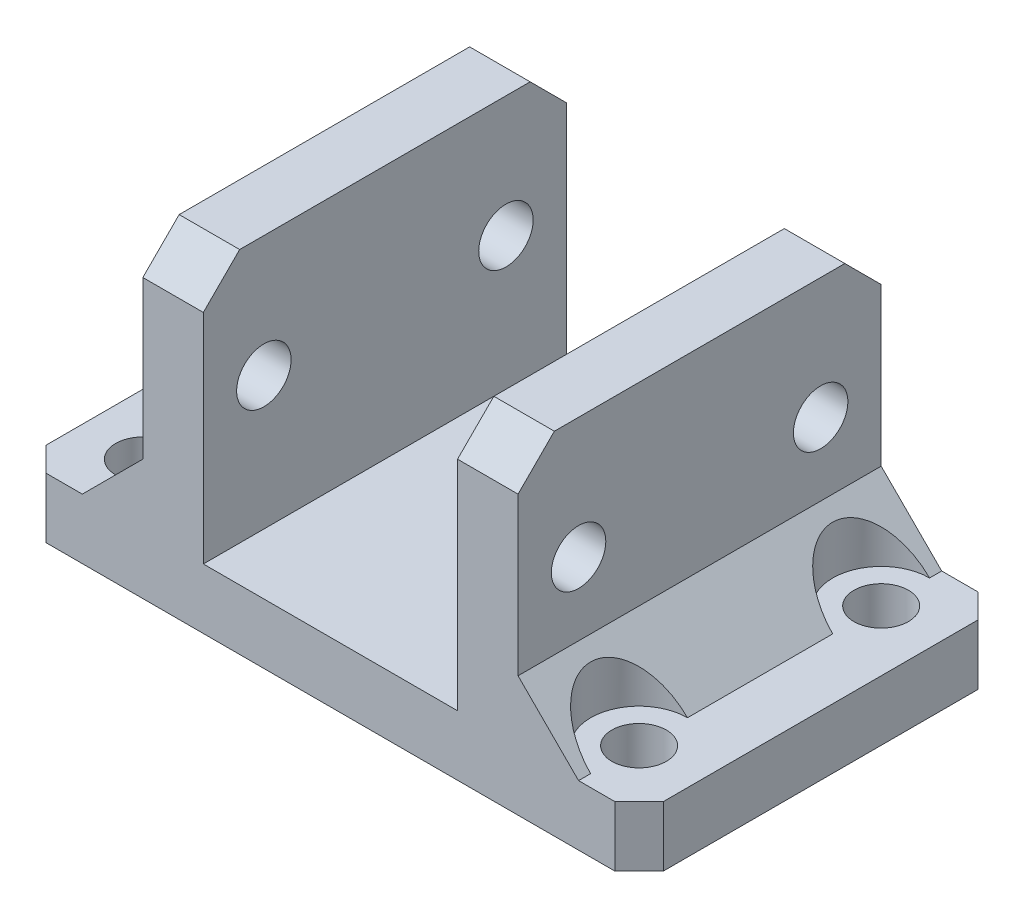
SolidWorks part; units mm, degrees
ref_plane "Front Plane" through (0, 0, 0) normal (0, 0, 1) x (1, 0, 0)
ref_plane "Top Plane" through (0, 0, 0) normal (0, 1, 0) x (1, 0, 0)
ref_plane "Right Plane" through (0, 0, 0) normal (1, 0, 0) x (0, 0, -1)
sketch "Sketch13" plane through (0, 0, 0) normal (0, 0, 1) x (1, 0, 0)
  line L2 (-11, 10) -> (-11, -11)
  line L3 (-11, -11) -> (10, -11)
  line L4 (10, 10) -> (10, -11)
  line L5 (-16, -11) -> (-26, -11)
  line L7 (10, -11) -> (-11, -11)
  line L8 (15, -11) -> (15, 10)
  line L9 (15, 10) -> (10, 10)
  line L10 (-16, -11) -> (-16, 10)
  line L13 (-11, 10) -> (-16, 10)
  line L14 (25, -15.9758) -> (-26, -15.9758)
  line L15 (25, -15.9758) -> (25, -11)
  line L16 (25, -11) -> (15, -11)
  line L17 (-26, -15.9758) -> (-26, -11)
  line L22 (10, -11) -> (-11, -11)
  point P0 (0, 0)
  point P6 (0, 0)
  point P13 (0, -12.4879)
  dimension "D1" = 21
  dimension "D2" = 21
  dimension "D3" = 10
  dimension "D4" = 5
  dimension "D5" = 5
  dimension "D6" = 10
extrude "Boss-Extrude1" add sketch "Sketch13" against normal blind 30 contours L17 L14 L15 L16 L8 L9 L4 L3 L2 L13 L10 L5 region at (-11.5723, -0.5, 0)
sketch "Sketch14" plane through (0, -11, 0) normal (0, 1, 0) x (1, 0, 0)
  line L0 (15, 30) -> (25, 30)
  line L2 (25, 0) -> (15, 0) construction
  line L3 (15, 0) -> (25, 0)
  line L4 (25, 30) -> (25, 0) construction
  line L6 (20, 30) -> (20, 0)
  line L10 (-26, 30) -> (-26, 0) construction
  circle A0 centre (20, 25) radius 2.25
  circle A1 centre (20, 5) radius 2.25
  circle A2 centre (-21, 5) radius 2.25
  circle A3 centre (-21, 25) radius 2.25
  circle A4 centre (20, 25) radius 4
  circle A5 centre (20, 5) radius 4
  circle A6 centre (-21, 5) radius 4
  circle A7 centre (-21, 25) radius 4
  dimension "D1" = 5
  dimension "D3" = 5
  dimension "D2" = 5
  dimension "D4" = 5
  dimension "D5" = 5
  dimension "D8" = 5
sketch "Sketch15" plane through (15, 0, 0) normal (1, 0, 0) x (0, 0, -1)
  line L0 (0, 0) -> (30, 0) construction
  line L1 (30, -11) -> (30, 10) construction
  line L2 (0, -11) -> (0, 10) construction
  circle A0 centre (5, 0) radius 2.25
  circle A1 centre (25, 0) radius 2.25
  dimension "D1" = 5
  dimension "D2" = 5
extrude "Cut-Extrude1" cut sketch "Sketch15" against normal blind 31
extrude "Cut-Extrude2" cut sketch "Sketch14" against normal blind 5 contours A3 | A2 | A0 | A0 | A1 | A1 region at (20.9549, -11, -25) region at (19.0451, -11, -25) region at (20.9549, -11, -5) region at (19.0451, -11, -5) region at (-21, -11, -5) region at (-21, -11, -25)
chamfer "Chamfer2" distance 3 angle 45 4 edges at (-13.5, 10, 0) (12.5, 10, 0) (-13.5, 10, -30) (12.5, 10, -30)
chamfer "Chamfer3" distance 2 angle 45 4 edges at (25, -13.4879, -30) (25, -13.4879, 0) (-26, -13.4879, 0) (-26, -13.4879, -30)
sketch "Sketch20" plane through (0, -15.9758, 0) normal (0, -1, 0) x (1, 0, 0)
  line L1 (-21, -5) -> (20, -5)
  line L2 (-21, -5) -> (-21, -25)
  line L3 (-21, -25) -> (20, -25)
  line L4 (20, -5) -> (20, -25)
chamfer "Chamfer4" distance 5 angle 45 2 edges at (-16, -11, -15) (15, -11, -15)
extrude "Cut-Extrude3" cut sketch "Sketch14<7>" along normal blind 10 contours A7 A3 | A6 A2 | L6 A5 A1 | L6 A4 A0 | L6 A4 A0 | L6 A5 A1 region at (22.7652, -11, -27.7652) region at (22.7652, -11, -7.7652) region at (19.9106, -11, -8.125) region at (19.9106, -11, -28.125) region at (-24.8869, -11, -5) region at (-24.8869, -11, -25)
sketch "Sketch14<7>" plane through (0, -11, 0) normal (0, 1, 0) x (1, 0, 0) same geometry as "Sketch14"
